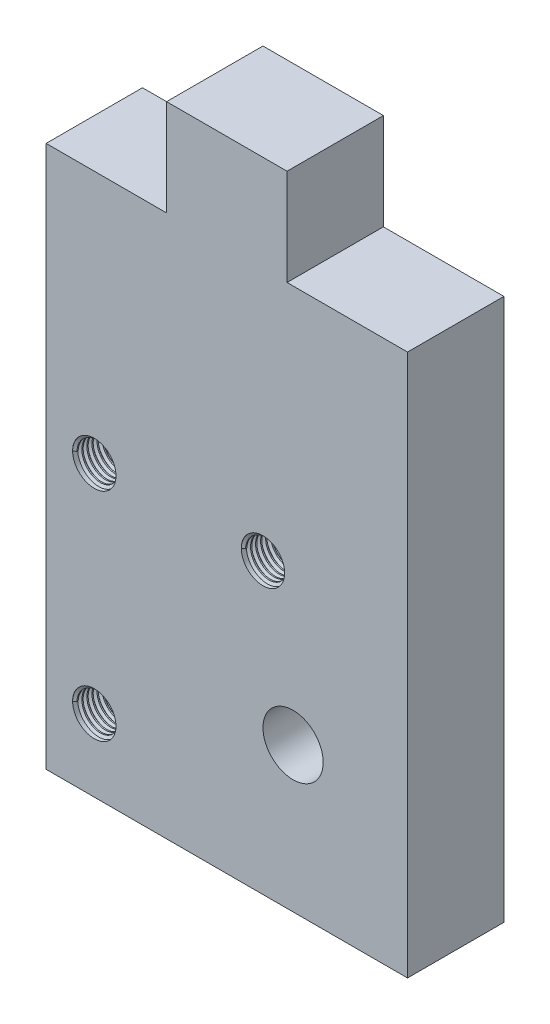
SolidWorks part; units mm, degrees
ref_plane "Front Plane" through (0, 0, 0) normal (0, 0, 1) x (1, 0, 0)
ref_plane "Top Plane" through (0, 0, 0) normal (0, 1, 0) x (1, 0, 0)
ref_plane "Right Plane" through (0, 0, 0) normal (1, 0, 0) x (0, 0, -1)
sketch "Sketch1" plane through (0, 0, 0) normal (0, 0, 1) x (1, 0, 0)
  line L0 (0, 57.15) -> (12.7, 57.15)
  line L1 (0, 0) -> (38.1, 0)
  line L5 (12.7, 57.15) -> (12.7, 67.31)
  line L6 (12.7, 67.31) -> (25.4, 67.31)
  line L7 (25.4, 67.31) -> (25.4, 57.15)
  line L8 (25.4, 57.15) -> (38.1, 57.15)
  line L9 (0, 57.15) -> (0, 0)
  line L10 (38.1, 57.15) -> (38.1, 0)
  line L11 (0, 74.3071) -> (10.16, 74.3071) construction
  line L12 (10.16, 74.3071) -> (10.16, 25.4) construction
  circle A0 centre (5.08, 7.62) radius 2.286
  circle A1 centre (5.08, 30.48) radius 2.286
  circle A2 centre (26.035, 15.24) radius 3.175
  circle A3 centre (22.86, 30.48) radius 2.286
  point P11 (29.21, 15.24)
  point P12 (22.86, 15.24)
  dimension "D3" = 7.62
  dimension "D5" = 4.572
  dimension "D6" = 4.572
  dimension "D8" = 29.21
  dimension "D9" = 12.7
  dimension "D10" = 10.16
  dimension "D13" = 17.78
  dimension "D14" = 4.572
  dimension "D1" = 38.1
  dimension "D2" = 5.08
  dimension "D4" = 22.86
  dimension "D7" = 22.86
  dimension "D11" = 10.16
  dimension "D12" = 25.4
  dimension "D15" = 5.08
extrude "Boss-Extrude1" add sketch "Sketch1" along normal blind 10.16
thread "Thread1" pitch 0.5292 method extrude profile "Thread Profile1" start angle 0, offset 0, length 9.652, pitch 0.5292, diameter 4.572
ref_plane "Plane1" through (2.794, 7.62, 10.16) normal (0, -1, 0) x (-1, 0, 0)
sketch "Thread Profile1" plane through (2.794, 7.62, 10.16) normal (0, -1, 0) x (-1, 0, 0)
  line L0 (0, 0) -> (0, 0.5292) construction
  line L11 (0, 0) -> (0, 0.463)
  line L12 (0, 0.463) -> (-0.2864, 0.2977)
  line L13 (-0.2864, 0.2977) -> (-0.2864, 0.1654)
  line L15 (-0.2864, 0.1654) -> (0, 0)
  line L17 (-0.2864, 0.2315) -> (0, 0.2315) construction
  point P2 (0, 0)
  dimension "Pitch" = 0.5292
  dimension "Profile_Angle" = 60
  dimension "Profile_Land" = 0.1323
  dimension "Profile_Height" = 0.2864
thread "Thread2" pitch 0.5292 method extrude profile "Thread Profile2" start angle 0, offset 0, length 9.652, pitch 0.5292, diameter 4.572
ref_plane "Plane2" through (2.794, 30.48, 10.16) normal (0, -1, 0) x (-1, 0, 0)
sketch "Thread Profile2" plane through (2.794, 30.48, 10.16) normal (0, -1, 0) x (-1, 0, 0)
  line L0 (0, 0) -> (0, 0.5292) construction
  line L11 (0, 0) -> (0, 0.463)
  line L12 (0, 0.463) -> (-0.2864, 0.2977)
  line L13 (-0.2864, 0.2977) -> (-0.2864, 0.1654)
  line L15 (-0.2864, 0.1654) -> (0, 0)
  line L17 (-0.2864, 0.2315) -> (0, 0.2315) construction
  point P2 (0, 0)
  dimension "Pitch" = 0.5292
  dimension "Profile_Angle" = 60
  dimension "Profile_Land" = 0.1323
  dimension "Profile_Height" = 0.2864
thread "Thread3" pitch 0.5292 method extrude profile "Thread Profile3" start angle 0, offset 0, length 9.652, pitch 0.5292, diameter 4.572
ref_plane "Plane3" through (20.574, 30.48, 10.16) normal (0, -1, 0) x (-1, 0, 0)
sketch "Thread Profile3" plane through (20.574, 30.48, 10.16) normal (0, -1, 0) x (-1, 0, 0)
  line L0 (0, 0) -> (0, 0.5292) construction
  line L11 (0, 0) -> (0, 0.463)
  line L12 (0, 0.463) -> (-0.2864, 0.2977)
  line L13 (-0.2864, 0.2977) -> (-0.2864, 0.1654)
  line L15 (-0.2864, 0.1654) -> (0, 0)
  line L17 (-0.2864, 0.2315) -> (0, 0.2315) construction
  point P2 (0, 0)
  dimension "Pitch" = 0.5292
  dimension "Profile_Angle" = 60
  dimension "Profile_Land" = 0.1323
  dimension "Profile_Height" = 0.2864
